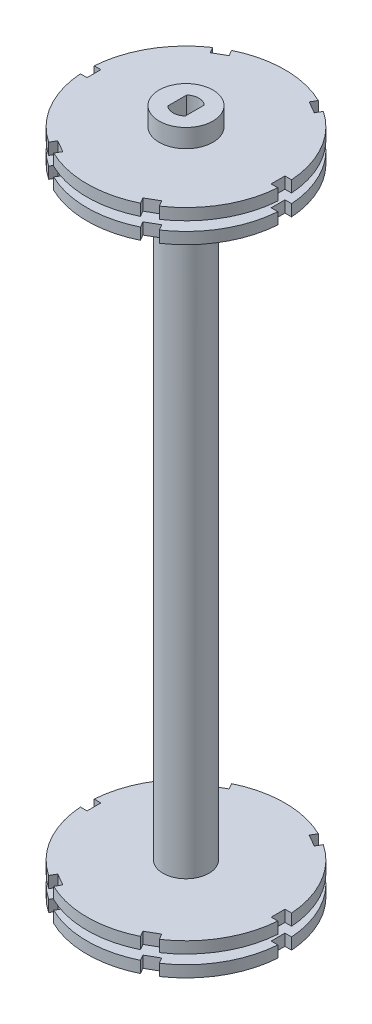
SolidWorks part; units mm, degrees
note: '?' marks a value the reader was unsure of.
ref_plane "Front Plane" through (0, 0, 0) normal (0, 0, 1) x (1, 0, 0)
ref_plane "Top Plane" through (0, 0, 0) normal (0, 1, 0) x (1, 0, 0)
ref_plane "Right Plane" through (0, 0, 0) normal (1, 0, 0) x (0, 0, -1)
sketch "Sketch1" plane through (0, 0, 0) normal (0, 1, 0) x (1, 0, 0)
  line L0 (1.9, 2.0567) -> (1.9, -2.0567)
  line L1 (-1.9, -2.0567) -> (-1.9, 2.0567)
  line L2 (-1.9, 2.0567) -> (-1.9, 5.5329)
  line L3 (1.9, 2.0567) -> (1.9, 5.5329)
  line L4 (-1.9, -2.0567) -> (-1.9, -5.5329)
  line L5 (1.9, -2.0567) -> (1.9, -5.5329)
  circle A0 centre (0, 0) radius 2.8
  circle A1 centre (0, 0) radius 5.85
  dimension "D1" = 5.6
  dimension "D4" = 11.7
  dimension "D2" = 1.9
  dimension "D3" = 1.9
extrude "Boss-Extrude1" add sketch "Sketch1" along normal blind 6.5 contours L2 A1 L4 A0 | L3 A1 L2 A0 | L5 A1 L3 A0 | L4 A1 L5 A0 | L1 A0 | L0 A0
sketch "Sketch2" plane through (0, 6.5, 0) normal (0, 1, 0) x (1, 0, 0)
  circle A0 centre (0, 0) radius 21.5
  dimension "D1" = 43
extrude "Boss-Extrude2" add sketch "Sketch2" against normal blind 2.5
sketch "Sketch3" plane through (0, 4, 0) normal (0, -1, 0) x (1, 0, 0)
  line L2 (-1.9, 2.0567) -> (-1.9, -2.0567)
  line L3 (1.9, -2.0567) -> (1.9, 2.0567)
  line L4 (-1.9, 2.0567) -> (-1.9, -2.0567)
  line L5 (1.9, -2.0567) -> (1.9, 2.0567)
  arc A2 (1.9, 2.0567) -> (-1.9, 2.0567) centre (0, 0) ccw
  arc A3 (-1.9, -2.0567) -> (1.9, -2.0567) centre (0, 0) ccw
  arc A4 (1.9, 2.0567) -> (-1.9, 2.0567) centre (0, 0) ccw
  arc A5 (-1.9, -2.0567) -> (1.9, -2.0567) centre (0, 0) ccw
  dimension "D1" = 0
extrude "Cut-Extrude1" cut sketch "Sketch3" against normal blind 8
sketch "Sketch4" plane through (0, 6.5, 0) normal (0, 1, 0) x (1, 0, 0)
  line L5 (-53.8948, 0) -> (53.8948, 0) construction
  line L6 (0, 31.6457) -> (0, -31.6457) construction
  line L7 (11.299, -16.5705) -> (12.799, -19.1686)
  line L9 (20, 1.5) -> (23, 1.5)
  line L10 (20, 1.5) -> (20, -1.5)
  line L11 (20, -1.5) -> (23, -1.5)
  line L12 (23, 1.5) -> (23, -1.5)
  line L13 (20, 1.5) -> (23, -1.5) construction
  line L14 (20, -1.5) -> (23, 1.5) construction
  line L29 (11.299, -16.5705) -> (8.701, -18.0705)
  line L30 (8.701, -18.0705) -> (10.201, -20.6686)
  line L35 (12.799, -19.1686) -> (10.201, -20.6686)
  line L36 (11.299, -16.5705) -> (10.201, -20.6686) construction
  line L41 (8.701, -18.0705) -> (12.799, -19.1686) construction
  line L42 (-26.9474, 46.6742) -> (26.9474, -46.6742) construction
  line L43 (-8.701, -18.0705) -> (-10.201, -20.6686)
  line L44 (-8.701, -18.0705) -> (-11.299, -16.5705)
  line L45 (-11.299, -16.5705) -> (-12.799, -19.1686)
  line L46 (-10.201, -20.6686) -> (-12.799, -19.1686)
  line L47 (-8.701, -18.0705) -> (-12.799, -19.1686) construction
  line L48 (-11.299, -16.5705) -> (-10.201, -20.6686) construction
  line L49 (26.9474, 46.6742) -> (-26.9474, -46.6742) construction
  line L50 (-20, -1.5) -> (-23, -1.5)
  line L51 (-20, -1.5) -> (-20, 1.5)
  line L52 (-20, 1.5) -> (-23, 1.5)
  line L53 (-23, -1.5) -> (-23, 1.5)
  line L54 (-20, -1.5) -> (-23, 1.5) construction
  line L55 (-20, 1.5) -> (-23, -1.5) construction
  line L56 (53.8948, 0) -> (-53.8948, 0) construction
  line L57 (-11.299, 16.5705) -> (-12.799, 19.1686)
  line L58 (-11.299, 16.5705) -> (-8.701, 18.0705)
  line L59 (-8.701, 18.0705) -> (-10.201, 20.6686)
  line L60 (-12.799, 19.1686) -> (-10.201, 20.6686)
  line L61 (-11.299, 16.5705) -> (-10.201, 20.6686) construction
  line L62 (-8.701, 18.0705) -> (-12.799, 19.1686) construction
  line L63 (26.9474, -46.6742) -> (-26.9474, 46.6742) construction
  line L64 (8.701, 18.0705) -> (10.201, 20.6686)
  line L65 (8.701, 18.0705) -> (11.299, 16.5705)
  line L66 (11.299, 16.5705) -> (12.799, 19.1686)
  line L67 (10.201, 20.6686) -> (12.799, 19.1686)
  line L68 (8.701, 18.0705) -> (12.799, 19.1686) construction
  line L69 (11.299, 16.5705) -> (10.201, 20.6686) construction
  line L70 (-26.9474, -46.6742) -> (26.9474, 46.6742) construction
  circle A0 centre (0, 0) radius 21.5 construction
  point P3 (0, 0)
  point P8 (0, 0)
  point P12 (21.5, 0)
  point P19 (10.75, -18.6195)
  point P26 (-10.75, -18.6195)
  point P33 (-21.5, 0)
  point P40 (-10.75, 18.6195)
  point P47 (10.75, 18.6195)
  dimension "D4" = 3
  dimension "D5" = 3
ref_axis "Axis1" through (0, 6.5, 0) along (0, -1, 0)?
extrude "Cut-Extrude2" cut sketch "Sketch4" against normal blind 10
sketch "Sketch5" plane through (0, 6.5, 0) normal (0, 1, 0) x (1, 0, 0)
  circle A0 centre (0, 0) radius 5
  dimension "D1" = 10
extrude "Boss-Extrude3" add sketch "Sketch5" along normal blind 140
ref_plane "Plane1" through (0, 76.5, 0) normal (0, 1, 0) x (1, 0, 0)
mirror "Mirror1" about plane through (0, 76.5, 0) normal (0, 1, 0) of "Boss-Extrude2"
mirror "Mirror2" about plane through (0, 76.5, 0) normal (0, 1, 0) of "Boss-Extrude1"
ref_plane "Plane2" through (0, 7.5, 0) normal (0, 1, 0) x (1, 0, 0)
mirror "Mirror3" about plane through (0, 7.5, 0) normal (0, 1, 0) of "Cut-Extrude2", "Boss-Extrude2", "Cut-Extrude1"
sketch "Sketch6" plane through (0, 11, 0) normal (0, -1, 0) x (1, 0, 0)
  line L2 (-1.9, 2.0567) -> (-1.9, -2.0567)
  line L3 (1.9, -2.0567) -> (1.9, 2.0567)
  line L4 (-1.9, 2.0567) -> (-1.9, -2.0567)
  line L5 (1.9, -2.0567) -> (1.9, 2.0567)
  arc A2 (1.9, 2.0567) -> (-1.9, 2.0567) centre (0, 0) ccw
  arc A3 (-1.9, -2.0567) -> (1.9, -2.0567) centre (0, 0) ccw
  arc A4 (1.9, 2.0567) -> (-1.9, 2.0567) centre (0, 0) ccw
  arc A5 (-1.9, -2.0567) -> (1.9, -2.0567) centre (0, 0) ccw
  dimension "D1" = 0
extrude "Cut-Extrude3" cut sketch "Sketch6" against normal blind 15
ref_plane "Plane3" through (0, 145.5, 0) normal (0, -1, 0) x (-1, 0, 0)
mirror "Mirror5" about plane through (0, 76.5, 0) normal (0, 1, 0) of "Cut-Extrude2"
mirror "Mirror6" about plane through (0, 145.5, 0) normal (0, -1, 0) of "Mirror5", "Mirror1"
sketch "Sketch7" plane through (0, 153, 0) normal (0, 1, 0) x (1, 0, 0)
